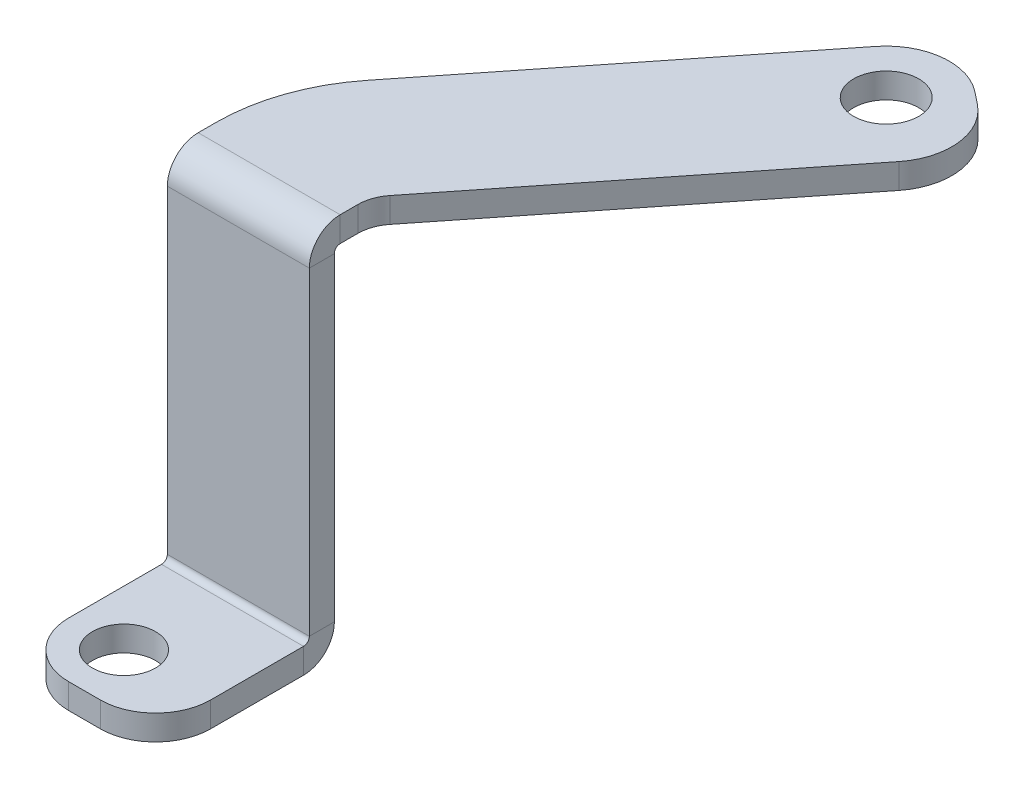
SolidWorks part; units mm, degrees
note: The reader was unsure of these and kept them because the rebuilt part matched: thickness of "Base-Flange1", "Edge-Flange1", "Edge-Flange2", "Sheet-Metal1", "Sheet-Metal2", "Sheet-Metal3", "Sheet-Metal4"; flange length of "Edge-Flange1", "Edge-Flange2".
material "Copper"
ref_plane "Front Plane" through (0, 0, 0) normal (0, 0, 1) x (1, 0, 0)
ref_plane "Top Plane" through (0, 0, 0) normal (0, 1, 0) x (1, 0, 0)
ref_plane "Right Plane" through (0, 0, 0) normal (1, 0, 0) x (0, 0, -1)
sketch "Sketch1" plane through (0, 0, 0) normal (0, 1, 0) x (1, 0, 0)
  line L0 (-7, 12.5) -> (-7, 0)
  line L2 (11, 12.5) -> (-7, 12.5)
  line L3 (0, -7) -> (4, -7)
  line L4 (11, 0) -> (11, 12.5)
  circle A0 centre (0, 0) radius 4
  arc A1 (-7, 0) -> (0, -7) centre (0, 0) ccw
  arc A2 (4, -7) -> (11, 0) centre (4, 0) ccw
  point P8 (6, -6.1108)
  point P10 (9.587, 12.5)
  dimension "D1" = 8
  dimension "D2" = 7
  dimension "D4" = 18
  dimension "D3" = 12.5
base flange "Base-Flange1" sketch "Sketch1" thickness 3.175 reverse thickness direction no parameters "D1"=0.7366
edge flange "Edge-Flange1" sketch "Sketch8" flange angle 90 flange length 45.0625 flange position material outside bend radius 0.7366 thickness 3.175 relief rectangular parameters "D6"=10
sketch "Sketch8" plane through (0, 0, -12.5) normal (0, 0, -1) x (-1, 0, 0)
  line L0 (-11, 0) -> (7, 0) construction
  line L1 (-11, 0) -> (7, 0)
  line L2 (-11, 0) -> (-11, 41.8875)
  line L3 (-11, 41.8875) -> (7, 41.8875)
  line L4 (7, 41.8875) -> (7, 0)
  line L5 (-25.25, 41.8875) -> (-40.25, 41.8875) construction
bend "EdgeBend1" bend radius 0.7366 bend angle 90 parameters "D5"=1
edge flange "Edge-Flange2" sketch "Sketch11" flange angle 90 flange length 6.175 flange position material outside bend radius 0.7366 thickness 3.175 relief rectangular parameters "D6"=10
sketch "Sketch11" plane through (0, 41.8875, -15.675) normal (0, 1, 0) x (1, 0, 0)
  line L0 (-7, 0) -> (11, 0) construction
  line L1 (-7, 0) -> (11, 0)
  line L2 (-7, 0) -> (-7, 3)
  line L4 (11, 3) -> (11, 0)
  line L7 (-7, 3) -> (11, 3)
  dimension "D1" = 3
bend "EdgeBend2" bend radius 0.7366 bend angle 90 parameters "D5"=2
sketch "Sketch12" plane through (0, 45.0625, 0) normal (0, 1, 0) x (1, 0, 0)
  line L0 (11, 18.675) -> (-7, 18.675)
  line L1 (-2.0624, 32.8494) -> (26.4814, 68.8484)
  line L2 (40.5857, 57.665) -> (12.0419, 21.666)
  line L3 (11, 16.4116) -> (11, 18.675) construction
  line L4 (-7, 18.675) -> (-7, 16.4116) construction
  line L5 (37.7204, 70.1466) -> (39.2875, 68.904)
  arc A0 (-7, 18.675) -> (-2.0624, 32.8494) centre (15.8141, 18.675) cw
  arc A2 (12.0419, 21.666) -> (11, 18.675) centre (15.8141, 18.675) ccw
  circle A3 centre (32.75, 63.878) radius 10 construction
  circle A4 centre (10.25, 63.878) radius 42.25 construction
  circle A5 centre (32.75, 63.878) radius 4.125
  arc A6 (26.4814, 68.8484) -> (37.7204, 70.1466) centre (32.75, 63.878) cw
  arc A7 (39.2875, 68.904) -> (40.5857, 57.665) centre (34.3171, 62.6354) cw
  dimension "D1" = 8.25
  dimension "D2" = 8
extrude "Boss-Extrude1" add sketch "Sketch12" against normal blind 3.175
sketch "Bend-Lines1" [suppressed] plane through (0, 0, 0) normal (0, 1, 0) x (1, 0, 0)
sketch "Bounding-Box1" [suppressed] plane through (0, 0, 0) normal (0, 1, 0) x (1, 0, 0)
sheet metal parameters "Sheet-Metal1" thickness 3.175 parameters "D1"=0.7366, "D7"=2
flat pattern "Flat-Pattern1" [suppressed]
sketch "Bend-Lines2" plane through (0, 0, 0) normal (0, 1, 0) x (1, 0, 0)
sketch3d "Bounding-Box2" [suppressed]
  line L0 (7, 12.5, 0) -> (7, -7, 0) construction
  line L1 (-7, 12.5, 0) -> (-7, -7, 0) construction
  line L2 (7, 12.5, 0) -> (-7, 12.5, 0) construction
  line L3 (7, -7, 0) -> (-7, -7, 0) construction
sheet metal parameters "Sheet-Metal2" thickness 3.175 parameters "D1"=0.7366, "D7"=2
flat pattern "Flat-Pattern1"
sketch "Bend-Lines2" plane through (0, 0, 0) normal (0, 1, 0) x (1, 0, 0)
  line L0 (7, 13.1273) -> (-7, 13.1273) construction
  line L1 (7, 13.1273) -> (-7, 13.1273) construction
sketch3d "Bounding-Box2" [suppressed]
  line L0 (7, 56.8171, 0) -> (7, -7, 0) construction
  line L1 (-7, 56.8171, 0) -> (-7, -7, 0) construction
  line L2 (7, 56.8171, 0) -> (-7, 56.8171, 0) construction
  line L3 (7, -7, 0) -> (-7, -7, 0) construction
bend of the flat pattern "Flatten-<EdgeBend1>1"
sheet metal parameters "Sheet-Metal3" thickness 3.175 parameters "D1"=0.7366, "D7"=2
flat pattern "Flat-Pattern1"
sketch "Bend-Lines2" plane through (0, 0, 0) normal (0, 1, 0) x (1, 0, 0)
  line L0 (7, 13.1273) -> (-7, 13.1273) construction
  line L1 (7, 13.1273) -> (-7, 13.1273) construction
  line L2 (7, 57.4445) -> (-7, 57.4445) construction
  line L3 (7, 57.4445) -> (-7, 57.4445) construction
sketch3d "Bounding-Box2" [suppressed]
  line L0 (7, 61.0718, 0) -> (7, -7, 0) construction
  line L1 (-7, 61.0718, 0) -> (-7, -7, 0) construction
  line L2 (7, 61.0718, 0) -> (-7, 61.0718, 0) construction
  line L3 (7, -7, 0) -> (-7, -7, 0) construction
bend of the flat pattern "Flatten-<EdgeBend1>1"
bend of the flat pattern "Flatten-<EdgeBend2>1"
sheet metal parameters "Sheet-Metal4" thickness 3.175 parameters "D1"=0.7366, "D7"=2
flat pattern "Flat-Pattern1"
sketch "Bend-Lines2" plane through (0, 0, 0) normal (0, 1, 0) x (1, 0, 0)
  line L0 (11, 13.5887) -> (-7, 13.5887) construction
  line L1 (11, 13.5887) -> (-7, 13.5887) construction
  line L2 (11, 57.6537) -> (-7, 57.6537) construction
  line L3 (11, 57.6537) -> (-7, 57.6537) construction
sketch3d "Bounding-Box2" [suppressed]
  line L0 (44.474, 111.8117, 0) -> (8.3963, -9.7926, 0) construction
  line L1 (9.9138, 122.0651, 0) -> (-26.164, 0.4609, 0) construction
  line L2 (44.474, 111.8117, 0) -> (9.9138, 122.0651, 0) construction
  line L3 (8.3963, -9.7926, 0) -> (-26.164, 0.4609, 0) construction
bend of the flat pattern "Flatten-<EdgeBend1>1"
bend of the flat pattern "Flatten-<EdgeBend2>1"
